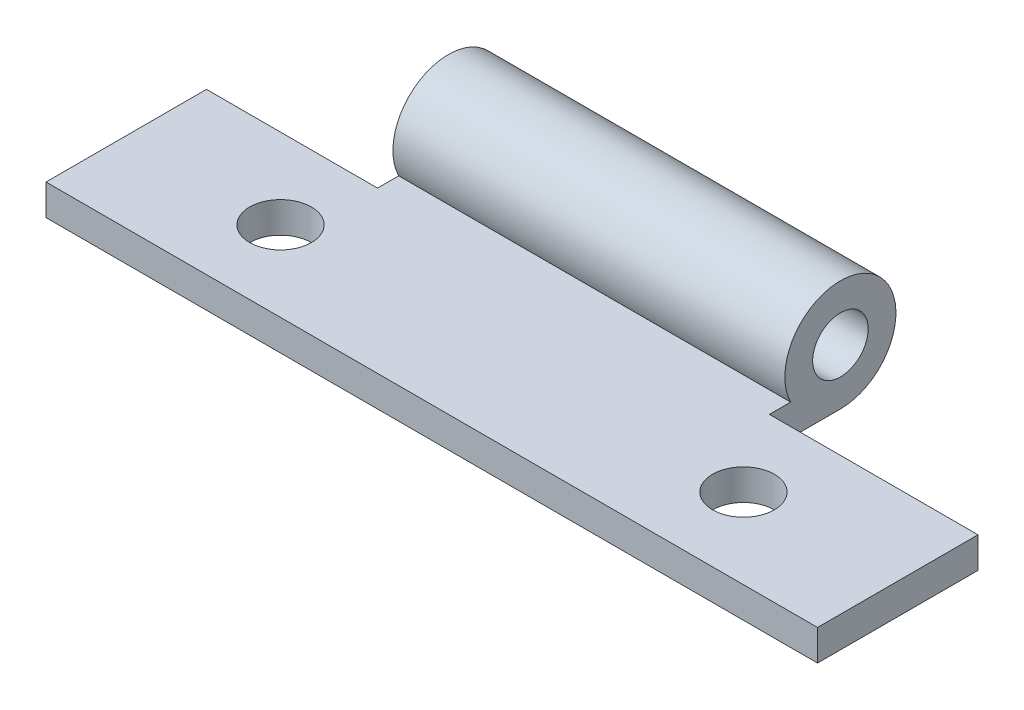
SolidWorks part; units mm, degrees
ref_plane "Front Plane" through (0, 0, 0) normal (0, 0, 1) x (1, 0, 0)
ref_plane "Top Plane" through (0, 0, 0) normal (0, 1, 0) x (1, 0, 0)
ref_plane "Right Plane" through (0, 0, 0) normal (1, 0, 0) x (0, 0, -1)
sketch "Sketch1" plane through (0, 0, 0) normal (1, 0, 0) x (0, 0, -1)
  line L2 (-6.7977, -1.2018) -> (-14.2977, -1.2018)
  line L3 (-14.2977, -1.2018) -> (-14.2977, -0.2018)
  line L4 (-14.2977, -0.2018) -> (-8.4101, -0.2018)
  arc A0 (-6.7977, -1.2018) -> (-8.4101, -0.2018) centre (-6.7977, 0.5982) ccw
  circle A1 centre (-6.7977, 0.5982) radius 0.9
  dimension "D1" = 3.6
  dimension "D2" = 1.8
  dimension "D4" = 7.5
  dimension "D5" = 1
extrude "Boss-Extrude1" add sketch "Sketch1" along normal blind 25
sketch "Sketch2" plane through (0, 0, 0) normal (0, 1, 0) x (1, 0, 0)
  line L0 (25, -4.9977) -> (0, -4.9977) construction
  line L1 (5.5413, -4.9977) -> (18.2413, -4.9977)
  line L2 (5.5413, -4.9977) -> (5.5413, -9.0977)
  line L3 (5.5413, -9.0977) -> (18.2413, -9.0977)
  line L4 (18.2413, -4.9977) -> (18.2413, -9.0977)
  line L5 (5.5413, -4.9977) -> (18.2413, -9.0977) construction
  line L6 (5.5413, -9.0977) -> (18.2413, -4.9977) construction
  line L7 (25, -8.4101) -> (25, -14.2977) construction
  line L8 (0, -4.9977) -> (5.5413, -4.9977)
  line L9 (0, -4.9977) -> (0, -9.0977)
  line L10 (0, -9.0977) -> (5.5413, -9.0977)
  line L11 (5.5413, -4.9977) -> (5.5413, -9.0977)
  line L12 (0, -4.9977) -> (5.5413, -9.0977) construction
  line L13 (0, -9.0977) -> (5.5413, -4.9977) construction
  line L14 (18.2413, -4.9977) -> (25, -4.9977)
  line L15 (18.2413, -4.9977) -> (18.2413, -9.0977)
  line L16 (18.2413, -9.0977) -> (25, -9.0977)
  line L17 (25, -4.9977) -> (25, -9.0977)
  line L18 (18.2413, -4.9977) -> (25, -9.0977) construction
  line L19 (18.2413, -9.0977) -> (25, -4.9977) construction
  point P4 (11.8913, -7.0477)
  point P10 (21.6207, -7.0477)
  point P12 (2.7707, -7.0477)
  dimension "D1" = 4.1
  dimension "D2" = 12.7
extrude "Cut-Extrude1" cut sketch "Sketch2" against normal blind 25 and the other way blind 25 contours L9 L10 L2 L8 | L17 L14 L4 L16 region at (2.7707, 0, 7.0477) region at (21.6207, 0, 7.0477)
ref_plane "Plane1" through (0, -0.2018, 0) normal (0, 1, 0) x (1, 0, 0)
sketch "Sketch3" plane through (0, -0.2018, 0) normal (0, 1, 0) x (1, 0, 0)
  line L0 (5, -14.2977) -> (5, -11.6977)
  line L1 (25, -14.2977) -> (0, -14.2977) construction
  line L2 (0, -9.0977) -> (0, -14.2977) construction
  line L3 (0, -11.6977) -> (5, -11.6977)
  line L4 (12.5, -14.2977) -> (12.5, -8.7829) construction
  circle A0 centre (5, -11.6977) radius 1
  circle A1 centre (20, -11.6977) radius 1
  dimension "D2" = 2
  dimension "D1" = 5
extrude "Cut-Extrude2" cut sketch "Sketch3" against normal blind 25 and the other way blind 25 contours L3 A0 L0 | L0 A0 L3 | A1 region at (4.5756, -0.2018, 12.1221) region at (5.1415, -0.2018, 11.5562) region at (20, -0.2018, 11.6977)
